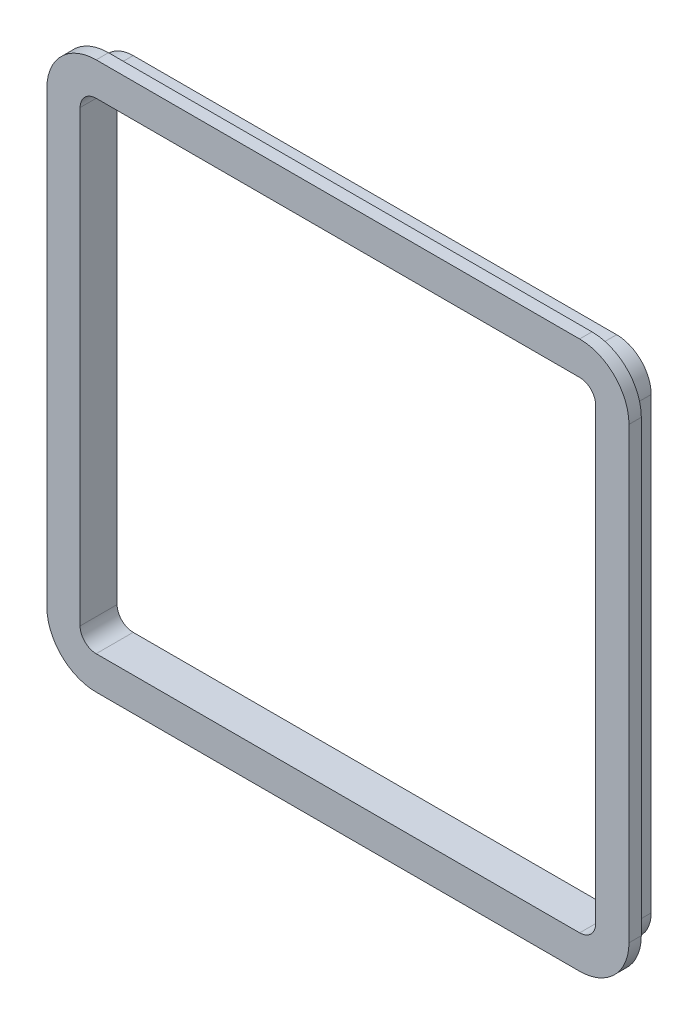
SolidWorks part; units mm, degrees
ref_plane "Front Plane" through (0, 0, 0) normal (0, 0, 1) x (1, 0, 0)
ref_plane "Top Plane" through (0, 0, 0) normal (0, 1, 0) x (1, 0, 0)
ref_plane "Right Plane" through (0, 0, 0) normal (1, 0, 0) x (0, 0, -1)
sketch "Sketch1" plane through (0, 0, 0) normal (0, 0, 1) x (1, 0, 0)
  line L5 (-20.9, 18.2) -> (-20.9, -18.2)
  line L6 (-19.6, -19.5) -> (19.6, -19.5)
  line L7 (20.9, -18.2) -> (20.9, 18.2)
  line L8 (19.6, 19.5) -> (-19.6, 19.5)
  line L9 (22.4, -18.2) -> (22.4, 18.2)
  line L10 (19.6, 21) -> (-19.6, 21)
  line L11 (-22.4, 18.2) -> (-22.4, -18.2)
  line L12 (-19.6, -21) -> (19.6, -21)
  line L13 (22.4, -18.2) -> (22.4, 18.2)
  line L14 (19.6, 21) -> (-19.6, 21)
  line L15 (-22.4, 18.2) -> (-22.4, -18.2)
  line L16 (-19.6, -21) -> (19.6, -21)
  arc A7 (-19.6, 19.5) -> (-20.9, 18.2) centre (-19.6, 18.2) ccw
  arc A8 (-20.9, -18.2) -> (-19.6, -19.5) centre (-19.6, -18.2) ccw
  arc A9 (19.6, -19.5) -> (20.9, -18.2) centre (19.6, -18.2) ccw
  arc A10 (20.9, 18.2) -> (19.6, 19.5) centre (19.6, 18.2) ccw
  arc A11 (19.6, -21) -> (22.4, -18.2) centre (19.6, -18.2) ccw
  arc A12 (22.4, 18.2) -> (19.6, 21) centre (19.6, 18.2) ccw
  arc A13 (-19.6, 21) -> (-22.4, 18.2) centre (-19.6, 18.2) ccw
  arc A14 (-22.4, -18.2) -> (-19.6, -21) centre (-19.6, -18.2) ccw
  arc A15 (19.6, -21) -> (22.4, -18.2) centre (19.6, -18.2) ccw
  arc A16 (22.4, 18.2) -> (19.6, 21) centre (19.6, 18.2) ccw
  arc A17 (-19.6, 21) -> (-22.4, 18.2) centre (-19.6, 18.2) ccw
  arc A18 (-22.4, -18.2) -> (-19.6, -21) centre (-19.6, -18.2) ccw
  dimension "D1" = 0.2
  dimension "D2" = 1.5
extrude "Boss-Extrude1" add sketch "Sketch1" along normal up to surface (2 mm away)
sketch "Sketch2" plane through (0, 0, 2) normal (0, 0, 1) x (1, 0, 0)
  line L0 (-19.6, -19.5) -> (19.6, -19.5) construction
  line L1 (20.9, -18.2) -> (20.9, 18.2) construction
  line L2 (19.6, 19.5) -> (-19.6, 19.5) construction
  line L3 (-20.9, 18.2) -> (-20.9, -18.2) construction
  line L4 (-19.6, -22.2) -> (19.6, -22.2)
  line L5 (23.6, -18.2) -> (23.6, 18.2)
  line L6 (19.6, 22.2) -> (-19.6, 22.2)
  line L7 (-23.6, 18.2) -> (-23.6, -18.2)
  line L8 (-19.6, -22.2) -> (19.6, -22.2)
  line L9 (23.6, -18.2) -> (23.6, 18.2)
  line L10 (19.6, 22.2) -> (-19.6, 22.2)
  line L11 (-23.6, 18.2) -> (-23.6, -18.2)
  line L12 (-19.6, -19.5) -> (19.6, -19.5)
  line L13 (20.9, -18.2) -> (20.9, 18.2)
  line L14 (19.6, 19.5) -> (-19.6, 19.5)
  line L15 (-20.9, 18.2) -> (-20.9, -18.2)
  arc A0 (-20.9, -18.2) -> (-19.6, -19.5) centre (-19.6, -18.2) ccw construction
  arc A1 (19.6, -19.5) -> (20.9, -18.2) centre (19.6, -18.2) ccw construction
  arc A2 (20.9, 18.2) -> (19.6, 19.5) centre (19.6, 18.2) ccw construction
  arc A3 (-19.6, 19.5) -> (-20.9, 18.2) centre (-19.6, 18.2) ccw construction
  arc A4 (-23.6, -18.2) -> (-19.6, -22.2) centre (-19.6, -18.2) ccw
  arc A5 (19.6, -22.2) -> (23.6, -18.2) centre (19.6, -18.2) ccw
  arc A6 (23.6, 18.2) -> (19.6, 22.2) centre (19.6, 18.2) ccw
  arc A7 (-19.6, 22.2) -> (-23.6, 18.2) centre (-19.6, 18.2) ccw
  arc A8 (-23.6, -18.2) -> (-19.6, -22.2) centre (-19.6, -18.2) ccw
  arc A9 (19.6, -22.2) -> (23.6, -18.2) centre (19.6, -18.2) ccw
  arc A10 (23.6, 18.2) -> (19.6, 22.2) centre (19.6, 18.2) ccw
  arc A11 (-19.6, 22.2) -> (-23.6, 18.2) centre (-19.6, 18.2) ccw
  arc A12 (-20.9, -18.2) -> (-19.6, -19.5) centre (-19.6, -18.2) ccw
  arc A13 (19.6, -19.5) -> (20.9, -18.2) centre (19.6, -18.2) ccw
  arc A14 (20.9, 18.2) -> (19.6, 19.5) centre (19.6, 18.2) ccw
  arc A15 (-19.6, 19.5) -> (-20.9, 18.2) centre (-19.6, 18.2) ccw
  dimension "D1" = 0
extrude "Boss-Extrude2" add sketch "Sketch2" along normal blind 1
